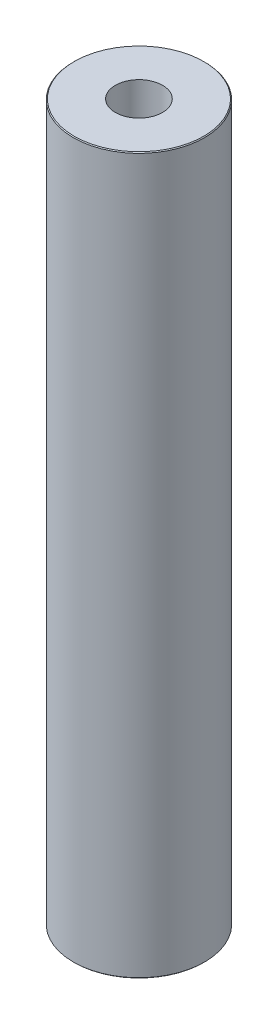
SolidWorks part; units mm, degrees
ref_plane "Front Plane" through (0, 0, 0) normal (0, 0, 1) x (1, 0, 0)
ref_plane "Top Plane" through (0, 0, 0) normal (0, 1, 0) x (1, 0, 0)
ref_plane "Right Plane" through (0, 0, 0) normal (1, 0, 0) x (0, 0, -1)
sketch "Sketch1" plane through (0, 0, 0) normal (0, 1, 0) x (1, 0, 0)
  circle A0 centre (0, 0) radius 55
  dimension "SHAFT_OD" = 110
extrude "Boss-Extrude1" add sketch "Sketch1" along normal blind 600
sketch "Sketch2" plane through (0, 0, 0) normal (0, 1, 0) x (1, 0, 0)
  circle A0 centre (0, 0) radius 19.7729
  dimension "BORE_D" = 39.5459
extrude "Cut-Extrude1" cut sketch "Sketch2" along normal through all
chamfer "Chamfer1" distance 0.701 angle 45 2 edges at (0, 600, 55) (0, 0, 55)
